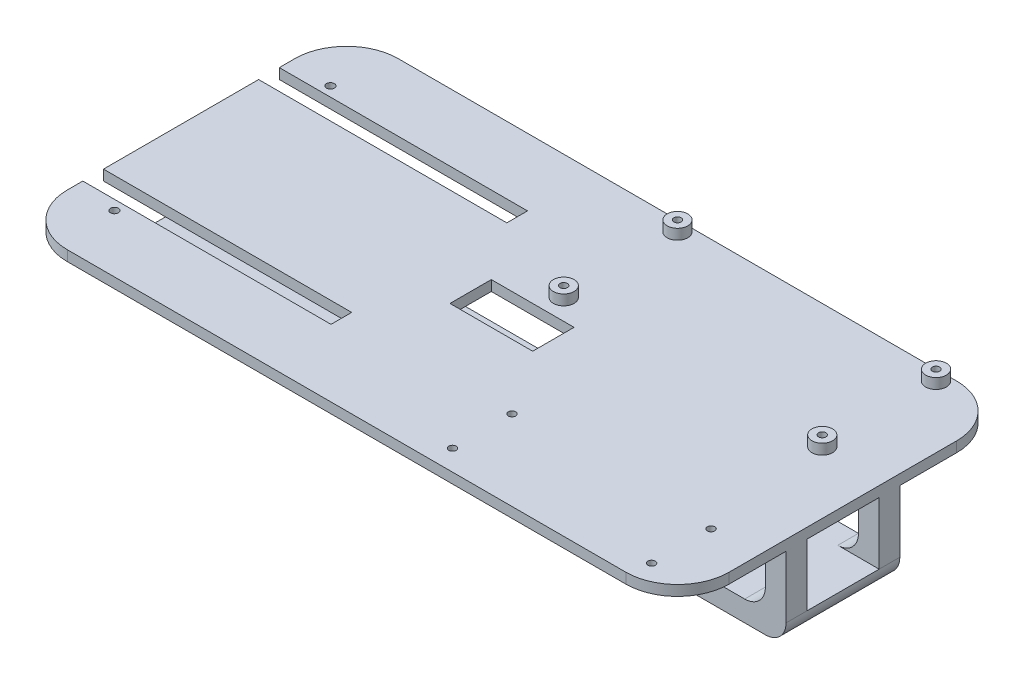
SolidWorks part; units mm, degrees
material "Polycarbonate"
ref_plane "Front Plane" through (0, 0, 0) normal (0, 0, 1) x (1, 0, 0)
ref_plane "Top Plane" through (0, 0, 0) normal (0, 1, 0) x (1, 0, 0)
ref_plane "Right Plane" through (0, 0, 0) normal (1, 0, 0) x (0, 0, -1)
sketch "Sketch1" plane through (0, 0, 0) normal (0, 1, 0) x (1, 0, 0)
  line L1 (-101.6, 17.4625) -> (101.6, 17.4625)
  line L2 (-101.6, 17.4625) -> (-101.6, -17.4625)
  line L3 (-101.6, -17.4625) -> (101.6, -17.4625)
  line L4 (101.6, 17.4625) -> (101.6, -17.4625)
  line L5 (-101.6, 17.4625) -> (101.6, -17.4625) construction
  line L6 (-101.6, -17.4625) -> (101.6, 17.4625) construction
  point P0 (0, 0)
  dimension "D1" = 34.925
  dimension "D2" = 203.2
extrude "Boss-Extrude1" add sketch "Sketch1" along normal blind 6.35
sketch "Sketch2" plane through (0, 6.35, 0) normal (0, 1, 0) x (1, 0, 0)
  line L0 (101.6, -17.4625) -> (101.6, 17.4625) construction
  line L1 (-101.6, -50.8) -> (101.6, -50.8)
  line L2 (-101.6, -50.8) -> (-101.6, 50.8)
  line L3 (-101.6, 50.8) -> (101.6, 50.8)
  line L4 (101.6, -50.8) -> (101.6, 50.8)
  line L5 (-101.6, -50.8) -> (101.6, 50.8) construction
  line L6 (-101.6, 50.8) -> (101.6, -50.8) construction
  point P0 (0, 0)
  dimension "D1" = 101.6
extrude "Boss-Extrude3" add sketch "Sketch2" along normal blind 3.175 from offset 19.05 separate body
sketch "Sketch3" plane through (0, 6.35, 0) normal (0, 1, 0) x (1, 0, 0)
  line L1 (101.6, -17.4625) -> (95.25, -17.4625)
  line L2 (101.6, -17.4625) -> (101.6, -11.1125)
  line L3 (101.6, -11.1125) -> (95.25, -11.1125)
  line L4 (95.25, -17.4625) -> (95.25, -11.1125)
  line L5 (101.6, 17.4625) -> (95.25, 17.4625)
  line L6 (101.6, 17.4625) -> (101.6, 11.1125)
  line L7 (101.6, 11.1125) -> (95.25, 11.1125)
  line L8 (95.25, 17.4625) -> (95.25, 11.1125)
  line L9 (-93.6625, -15.0813) -> (-87.3125, -15.0812)
  line L10 (-93.6625, -15.0813) -> (-93.6625, -10.3188)
  line L11 (-93.6625, -10.3188) -> (-87.3125, -10.3188)
  line L12 (-87.3125, -15.0812) -> (-87.3125, -10.3188)
  line L13 (-101.6, 17.4625) -> (-101.6, -17.4625) construction
  line L15 (-93.6625, 15.0813) -> (-87.3125, 15.0813)
  line L16 (-93.6625, 15.0813) -> (-93.6625, 10.3188)
  line L17 (-93.6625, 10.3188) -> (-87.3125, 10.3188)
  line L18 (-87.3125, 15.0813) -> (-87.3125, 10.3188)
  line L21 (-101.6, -17.4625) -> (101.6, -17.4625) construction
  line L22 (101.6, 17.4625) -> (-101.6, 17.4625) construction
  point P16 (-90.4875, -10.3188)
  point P23 (-87.3125, 12.7)
  point P25 (-90.4875, 15.0813)
  point P29 (-93.6625, -12.7)
  line M9 (101.6, -17.4625) -> (101.6, 17.4625)
  line M10 (101.6, 17.4625) -> (-101.6, 17.4625)
  line M12 (-101.6, -17.4625) -> (101.6, -17.4625)
  dimension "D1" = 6.35
  dimension "D2" = 11.1125
  dimension "D3" = 6.35
  dimension "D4" = 4.7625
  dimension "D5" = 11.1125
  dimension "D6" = 6.35
  dimension "D7" = 4.7625
  dimension "D8" = 4.7625
  dimension "D9" = 4.7625
extrude "Boss-Extrude4" add sketch "Sketch3" along normal up to next contours L4 L3 M12 M9 | L8 L7 M10 M9 region at (98.425, 6.35, -14.2875) region at (98.425, 6.35, 14.2875)
sketch "Sketch4" plane through (0, 28.575, 0) normal (0, 1, 0) x (1, 0, 0)
  line L0 (-101.6, 50.8) -> (-101.6, -50.8) construction
  line L1 (-101.6, -50.8) -> (101.6, -50.8) construction
  line L2 (-101.6, -30.1625) -> (-25.4, -30.1625)
  line L3 (-101.6, -30.1625) -> (-101.6, -23.8125)
  line L4 (-101.6, -23.8125) -> (-25.4, -23.8125)
  line L5 (-25.4, -30.1625) -> (-25.4, -23.8125)
  line L6 (0, 0) -> (-101.6, 0) construction
  line L7 (-25.4, 30.1625) -> (-25.4, 23.8125)
  line L8 (-101.6, 30.1625) -> (-25.4, 30.1625)
  line L9 (-101.6, 30.1625) -> (-101.6, 23.8125)
  line L10 (-101.6, 23.8125) -> (-25.4, 23.8125)
  dimension "D1" = 20.6375
  dimension "D2" = 6.35
  dimension "D3" = 76.2
extrude "Cut-Extrude1" cut sketch "Sketch4" against normal blind 3.175
sketch "Sketch5" plane through (101.6, 0, 0) normal (1, 0, 0) x (0, 0, -1)
  line L1 (14.8971, 25.4) -> (14.8971, 36.7665)
  line L3 (17.4625, 25.4) -> (17.4625, 0) construction
  line L5 (-10.1346, 32.004) -> (-10.1346, 25.4)
  line L6 (10.0076, 25.4) -> (10.0076, 32.004)
  line L7 (-14.8971, 25.4) -> (-10.1346, 25.4)
  line L8 (10.0076, 25.4) -> (14.8971, 25.4)
  line L11 (-50.8, 25.4) -> (-17.4625, 25.4) construction
  line L12 (-46.0375, 25.4) -> (-42.8625, 25.4)
  line L13 (-46.0375, 25.4) -> (-46.0375, 22.225)
  line L14 (-46.0375, 22.225) -> (-42.8625, 22.225)
  line L15 (-42.8625, 25.4) -> (-42.8625, 22.225)
  line L16 (-11.1125, 6.35) -> (11.1125, 6.35) construction
  line L21 (17.4625, 25.4) -> (50.8, 25.4) construction
  line L22 (-14.8971, 25.4) -> (-14.8971, 36.7665)
  line L23 (-50.8, 28.575) -> (-50.8, 25.4) construction
  line L24 (42.8625, 25.4) -> (46.0375, 25.4)
  line L25 (42.8625, 25.4) -> (42.8625, 22.225)
  line L26 (42.8625, 22.225) -> (46.0375, 22.225)
  line L27 (46.0375, 25.4) -> (46.0375, 22.225)
  line L28 (-14.8971, 36.7665) -> (-3.7846, 36.7665)
  line L29 (50.8, 28.575) -> (50.8, 25.4) construction
  line L30 (-3.7846, 36.7665) -> (-3.7846, 32.004)
  line L31 (-3.7846, 32.004) -> (-10.1346, 32.004)
  line L32 (14.8971, 36.7665) -> (3.6576, 36.7665)
  line L33 (3.6576, 36.7665) -> (3.6576, 32.004)
  line L34 (3.6576, 32.004) -> (10.0076, 32.004)
  line L35 (-17.4625, 25.4) -> (-17.4625, 0) construction
  point P31 (-46.0375, 23.8125)
  point P38 (17.4625, 12.7)
  dimension "D2" = 6.604
  dimension "D3" = 2.5654
  dimension "D4" = 3.175
  dimension "D5" = 3.175
  dimension "D6" = 4.7625
  dimension "D7" = 4.7625
  dimension "D8" = 3.175
  dimension "D9" = 3.175
  dimension "D10" = 19.05
  dimension "D11" = 4.7625
  dimension "D12" = 4.7625
  dimension "D13" = 6.35
  dimension "D14" = 4.8895
  dimension "D15" = 6.35
  dimension "D16" = 4.7625
  dimension "D17" = 2.5654
extrude "Boss-Extrude5" add sketch "Sketch5" against normal blind 3.175 from offset 190.5 contours L15 L14 L13 L12 | L27 L26 L25 L24 offset against normal yes
hole_wizard "#2 Clearance Hole1" positions "Sketch7" profile "Sketch8" hole size "#2" standard "ANSI Inch" end condition through all
sketch "Sketch7" plane through (0, 25.4, 0) normal (0, -1, 0) x (-1, 0, 0)
  line L12 (25.4, 30.1625) -> (101.6, 30.1625) construction
  line L13 (101.6, 50.8) -> (101.6, 30.1625) construction
  line L14 (101.6, -30.1625) -> (101.6, -50.8) construction
  line L15 (101.6, -30.1625) -> (25.4, -30.1625) construction
  point P20 (88.9, 33.147)
  point P69 (88.9, -33.147)
  dimension "D1" = 2.9845
  dimension "D2" = 12.7
  dimension "D3" = 12.7
  dimension "D4" = 2.9845
sketch "Sketch8" plane through (-88.9, 25.4, -33.147) normal (1, 0, 0) x (0, 0, -1)
  line L0 (0, 0) -> (0, 3.175)
  line L1 (0, 3.175) -> (1.2192, 3.175)
  line L2 (1.2192, 3.175) -> (1.2192, 0)
  line L5 (1.2192, 0) -> (0, 0)
  line L11 (0, -6.35) -> (0, 107.95) construction
  dimension "Thru Hole Dia." = 2.4384
  dimension "Thru Hole Depth" = 3.175
fillet "Fillet1" radius 15.875 2 edges at (101.6, 26.9875, -50.8) (101.6, 26.9875, 50.8)
fillet "Fillet2" radius 6.35 3 edges at (95.25, 6.35, 14.2875) (95.25, 6.35, -14.2875) (101.6, 0, 0)
hole_wizard "#4-40 Tapped Hole2" positions "Sketch12" profile "Sketch14" tap size "#4-40" standard "ANSI Inch" end condition through all
sketch "Sketch12" plane through (0, 25.4, 0) normal (0, -1, 0) x (-1, 0, 0)
  line L0 (-26.1937, -44.45) -> (-87.3125, -44.45) construction
  line L2 (101.6, -50.8) -> (-85.725, -50.8) construction
  line L3 (-101.6, -34.925) -> (-101.6, -17.4625) construction
  line L4 (-26.1937, -44.45) -> (-26.1937, -26.1937) construction
  line L6 (-26.1937, -26.1937) -> (-87.3125, -26.1938) construction
  line L7 (-87.3125, -26.1938) -> (-87.3125, -44.45) construction
  line L8 (101.6, -50.8) -> (-85.725, -50.8) construction
  point P0 (-87.3125, -44.45)
  point P3 (-87.3125, -26.1938)
  point P6 (-26.1937, -26.1937)
  point P9 (-26.1937, -44.45)
  dimension "D1" = 61.1187
  dimension "D2" = 6.35
  dimension "D3" = 14.2875
  dimension "D4" = 24.6062
sketch "Sketch14" plane through (87.3125, 25.4, 44.45) normal (1, 0, 0) x (0, 0, -1)
  line L0 (0, 0) -> (0, 3.175)
  line L1 (0, 3.175) -> (1.1303, 3.175)
  line L2 (1.1303, 3.175) -> (1.1303, 0)
  line L5 (1.1303, 0) -> (0, 0)
  line L11 (0, -6.35) -> (0, 107.95) construction
  dimension "Thru Tap Drill Dia." = 2.2606
  dimension "Thru Tap Drill Depth" = 3.175
cosmetic thread "Hole Thread5" parameters "D2"=2.8448
cosmetic thread "Hole Thread6" parameters "D2"=2.8448
cosmetic thread "Hole Thread7" parameters "D2"=2.8448
cosmetic thread "Hole Thread8" parameters "D2"=2.8448
sketch "Sketch15" plane through (0, 25.4, 0) normal (0, -1, 0) x (1, 0, 0)
  circle A0 centre (26.1937, 44.45) radius 3.175
  circle A1 centre (87.3125, 44.45) radius 3.175
  circle A2 centre (87.3125, 26.1938) radius 3.175
  circle A3 centre (26.1937, 26.1937) radius 3.175
  dimension "D1" = 6.35
extrude "Boss-Extrude6" add sketch "Sketch15" along normal blind 1.5875
hole_wizard "#4 Clearance Hole3" positions "Sketch19" profile "Sketch20" hole size "#4" standard "ANSI Inch" end condition through all
sketch "Sketch19" plane through (0, 25.4, 0) normal (0, 1, 0) x (1, 0, 0)
  point P0 (87.3125, -44.45)
  point P3 (87.3125, -26.1938)
  point P6 (26.1937, -26.1937)
  point P9 (26.1937, -44.45)
sketch "Sketch20" plane through (87.3125, 25.4, 44.45) normal (1, 0, 0) x (0, 0, 1)
  line L0 (0, 0) -> (0, 25.4)
  line L1 (0, 25.4) -> (1.6319, 25.4)
  line L2 (1.6319, 25.4) -> (1.6319, 0)
  line L5 (1.6319, 0) -> (0, 0)
  line L11 (0, -6.35) -> (0, 107.95) construction
  dimension "Thru Hole Dia." = 3.2639
  dimension "Thru Hole Depth" = 25.4
sketch "Sketch22" plane through (-101.6, 0, 0) normal (-1, 0, 0) x (0, 0, 1)
  line L5 (-17.4625, 0) -> (17.4625, 0) construction
  line L6 (17.0656, 0) -> (12.7476, 0)
  line L7 (17.0656, 0) -> (17.0656, -9.652)
  line L8 (17.0656, -9.652) -> (7.9851, -9.652)
  line L9 (12.7476, 0) -> (12.7476, -6.477)
  line L10 (17.4625, 6.35) -> (17.4625, 0) construction
  line L12 (7.9851, -9.652) -> (7.9851, -6.477)
  line L13 (7.9851, -6.477) -> (12.7476, -6.477)
  line L14 (0, 0) -> (0, -14.0919) construction
  line L15 (-7.9851, -6.477) -> (-12.7476, -6.477)
  line L16 (-7.9851, -9.652) -> (-7.9851, -6.477)
  line L17 (-12.7476, 0) -> (-12.7476, -6.477)
  line L18 (-17.0656, -9.652) -> (-7.9851, -9.652)
  line L19 (-17.0656, 0) -> (-17.0656, -9.652)
  line L20 (-17.0656, 0) -> (-12.7476, 0)
  dimension "D1" = 4.318
  dimension "D2" = 0.3969
  dimension "D3" = 9.652
  dimension "D4" = 3.175
  dimension "D5" = 4.7625
extrude "Boss-Extrude11" add sketch "Sketch22" against normal blind 4.318
fillet "Fillet10" 2 edges at (-99.441, -9.652, 7.9851) (-99.441, -6.477, 7.9851) type full round first side face at (-99.441, -9.652, 12.5254) second side face at (-99.441, -6.477, 10.3664) middle face at (-99.441, -8.0645, 7.9851)
fillet "Fillet11" 2 edges at (-99.441, -6.477, -7.9851) (-99.441, -9.652, -7.9851) type full round first side face at (-99.441, -6.477, -10.3664) second side face at (-99.441, -9.652, -12.5254) middle face at (-99.441, -8.0645, -7.9851)
fillet "Fillet12" radius 3.175 2 edges at (-99.441, -9.652, -17.0656) (-99.441, -9.652, 17.0656)
fillet "Fillet14" radius 15.875 2 edges at (-101.6, 26.9875, 50.8) (-101.6, 26.9875, -50.8)
sketch "Sketch23" plane through (0, 28.575, 0) normal (0, 1, 0) x (1, 0, 0)
  line L0 (101.6, -34.925) -> (101.6, 34.925) construction
  line L1 (82.55, 12.7) -> (3.175, 12.7) construction
  line L2 (82.55, 12.7) -> (82.55, 47.625) construction
  line L3 (82.55, 47.625) -> (3.175, 47.625) construction
  line L4 (3.175, 12.7) -> (3.175, 47.625) construction
  line L5 (85.725, 50.8) -> (-85.725, 50.8) construction
  circle A0 centre (3.175, 12.7) radius 3.175
  circle A1 centre (3.175, 47.625) radius 3.175
  circle A2 centre (82.55, 12.7) radius 3.175
  circle A3 centre (82.55, 47.625) radius 3.175
  dimension "D1" = 79.375
  dimension "D2" = 34.925
  dimension "D3" = 19.05
  dimension "D4" = 3.175
extrude "Boss-Extrude12" add sketch "Sketch23" along normal blind 3.175
sketch "Sketch26" plane through (0, 28.575, 0) normal (0, 1, 0) x (1, 0, 0)
  line L1 (-12.7, -6.35) -> (12.7, -6.35)
  line L2 (-12.7, -6.35) -> (-12.7, 6.35)
  line L3 (-12.7, 6.35) -> (12.7, 6.35)
  line L4 (12.7, -6.35) -> (12.7, 6.35)
  line L5 (-12.7, -6.35) -> (12.7, 6.35) construction
  line L6 (-12.7, 6.35) -> (12.7, -6.35) construction
  point P0 (0, 0)
  dimension "D1" = 25.4
  dimension "D2" = 12.7
extrude "Cut-Extrude2" cut sketch "Sketch26" against normal up to next
hole_wizard "#4-40 Tapped Hole3" positions "Sketch28" profile "Sketch29" tap size "#4-40" standard "ANSI Inch" end condition up to next
sketch "Sketch28" plane through (0, 31.75, 0) normal (0, 1, 0) x (1, 0, 0)
  point P0 (3.175, 47.625)
  point P3 (3.175, 12.7)
  point P6 (82.55, 12.7)
  point P9 (82.55, 47.625)
sketch "Sketch29" plane through (3.175, 31.75, -47.625) normal (1, 0, 0) x (0, 0, 1)
  line L0 (0, 0) -> (0, 6.35)
  line L1 (0, 6.35) -> (1.1303, 6.35)
  line L2 (1.1303, 6.35) -> (1.1303, 0)
  line L5 (1.1303, 0) -> (0, 0)
  line L11 (0, -6.35) -> (0, 107.95) construction
  dimension "Thru Tap Drill Dia." = 2.2606
  dimension "Thru Tap Drill Depth" = 6.35
cosmetic thread "Hole Thread9" parameters "D2"=2.8448
cosmetic thread "Hole Thread10" parameters "D2"=2.8448
cosmetic thread "Hole Thread11" parameters "D2"=2.8448
cosmetic thread "Hole Thread12" parameters "D2"=2.8448
